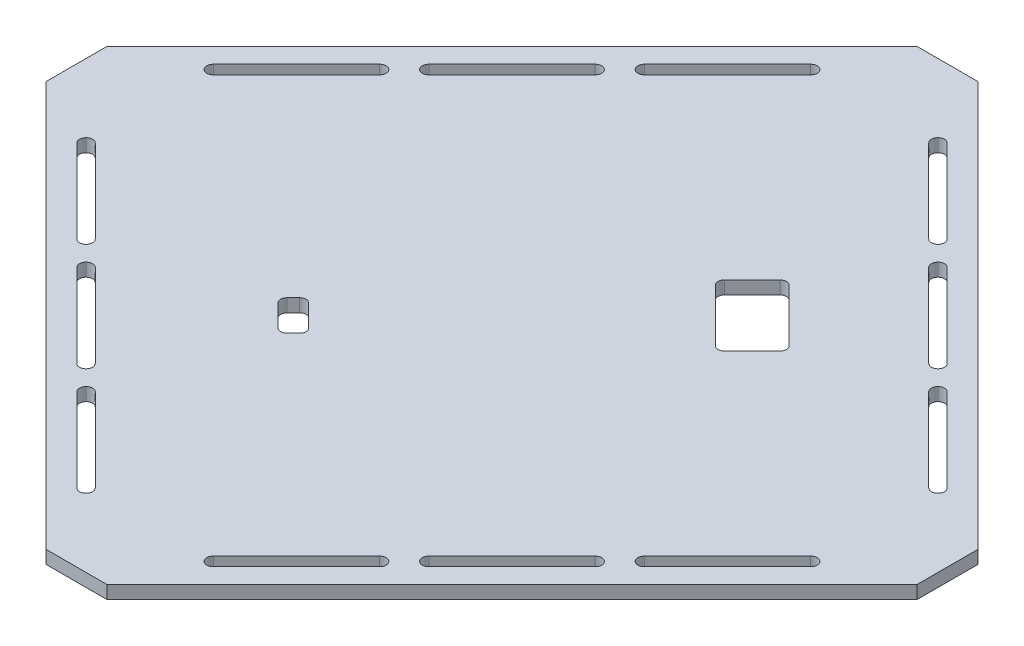
SolidWorks part; units mm, degrees
other "Top Plate" parameters "D1"=4.9724, "D2"=36.4956, "D3"=27.5828, "D4"=37.1524, "D5"=11.2108, "D6"=6.5652, "D8"=3.8454, "D7"=4
ref_plane "Front Plane" through (0, 0, 0) normal (0, 0, 1) x (1, 0, 0)
ref_plane "Top Plane" through (0, 0, 0) normal (0, 1, 0) x (1, 0, 0)
ref_plane "Right Plane" through (0, 0, 0) normal (1, 0, 0) x (0, 0, -1)
sketch "Sketch1" plane through (0, 0, 0) normal (0, 1, 0) x (1, 0, 0)
  line L0 (-7, 100) -> (7, 100)
  line L1 (7, 100) -> (100, 7)
  line L2 (100, 7) -> (100, -7)
  line L3 (100, -7) -> (7, -100)
  line L4 (7, -100) -> (-7, -100)
  line L5 (-7, -100) -> (-100, -7)
  line L6 (-100, -7) -> (-100, 7)
  line L7 (-100, 7) -> (-7, 100)
  point P11 (0, 100)
  point P13 (100, 0)
  dimension "D1" = 200
  dimension "D2" = 200
  dimension "D3" = 14
extrude "Main Plate" add sketch "Sketch1" along normal blind 3 contours L1 L2 L3 L4 L5 L6 L7 L0
sketch "Sketch2" plane through (0, 0, 0) normal (0, -1, 0) x (1, 0, 0)
  line L0 (7.7782, 16.9706) -> (16.9706, 7.7782)
  line L3 (16.9706, 7.7782) -> (19.0919, 9.8995)
  line L6 (19.0919, 9.8995) -> (9.8995, 19.0919)
  line L7 (9.8995, 19.0919) -> (7.7782, 16.9706)
  line L8 (0, 0) -> (53.5, 53.5) construction
  line L9 (100, 7) -> (7, 100) construction
  line L10 (16.9706, -7.7782) -> (7.7782, -16.9706)
  line L11 (9.8995, -19.0919) -> (19.0919, -9.8995)
  line L12 (19.0919, -9.8995) -> (16.9706, -7.7782)
  line L13 (7.7782, -16.9706) -> (9.8995, -19.0919)
  line L14 (-7.7782, -16.9706) -> (-16.9706, -7.7782)
  line L15 (-19.0919, -9.8995) -> (-9.8995, -19.0919)
  line L16 (-9.8995, -19.0919) -> (-7.7782, -16.9706)
  line L17 (-16.9706, -7.7782) -> (-19.0919, -9.8995)
  line L18 (-16.9706, 7.7782) -> (-7.7782, 16.9706)
  line L19 (-9.8995, 19.0919) -> (-19.0919, 9.8995)
  line L20 (-19.0919, 9.8995) -> (-16.9706, 7.7782)
  line L21 (-7.7782, 16.9706) -> (-9.8995, 19.0919)
  point P8 (14.4957, 14.4957)
  point P9 (12.3744, 12.3744)
  point P26 (0, 0)
  dimension "D1" = 3
  dimension "D2" = 13
  dimension "D3" = 17.5
  dimension "D4" = 4
extrude "Bottom Plate Connectors" add sketch "Sketch2" along normal blind 22
fillet "Remove Stress Concentrations" radius 2.5 12 edges at (-14.4957, 0, -14.4957) (-18.0312, 0, -8.8388) (-18.0312, 0, 8.8388) (8.8388, 0, 18.0312) (-14.4957, 0, 14.4957) (-8.8388, 0, 18.0312) (14.4957, 0, 14.4957) (18.0312, 0, -8.8388) (18.0312, 0, 8.8388) (-8.8388, 0, -18.0312) (14.4957, 0, -14.4957) (8.8388, 0, -18.0312)
sketch "Sketch3" plane through (0, 0, 0) normal (0, -1, 0) x (1, 0, 0)
  line L0 (30.4056, -16.2635) -> (38.8909, -24.7487)
  line L1 (38.8909, -24.7487) -> (24.7487, -38.8909)
  line L2 (24.7487, -38.8909) -> (16.2635, -30.4056)
  line L3 (16.2635, -30.4056) -> (30.4056, -16.2635)
  line L4 (16.2635, -16.2635) -> (53.5, -53.5) construction
  line L5 (22.6274, -9.8995) -> (9.8995, -22.6274) construction
  line L6 (7, -100) -> (100, -7) construction
  line L7 (-23.3345, 30.4056) -> (-19.799, 26.8701)
  line L8 (-19.799, 26.8701) -> (-26.8701, 19.799)
  line L9 (-26.8701, 19.799) -> (-30.4056, 23.3345)
  line L10 (-30.4056, 23.3345) -> (-23.3345, 30.4056)
  line L11 (-16.2635, 16.2635) -> (-53.5, 53.5) construction
  line L12 (-22.6274, 9.8995) -> (-9.8995, 22.6274) construction
  line L13 (-7, 100) -> (-100, 7) construction
  point P10 (23.3345, -23.3345)
  point P21 (-23.3345, 23.3345)
  dimension "D1" = 20
  dimension "D2" = 12
  dimension "D3" = 10
  dimension "D4" = 10
  dimension "D5" = 5
  dimension "D6" = 10
extrude "Wire Holes" cut sketch "Sketch3" against normal through all
sketch "Sketch4" plane through (0, 3, 0) normal (0, 1, 0) x (1, 0, 0)
  line L0 (14.6091, 85.3198) -> (35.8223, 64.1066)
  line L1 (35.8223, 64.1066) -> (33.701, 61.9853)
  line L2 (33.701, 61.9853) -> (12.4878, 83.1985)
  line L3 (12.4878, 83.1985) -> (14.6091, 85.3198)
  line L4 (39.3579, 60.5711) -> (60.5711, 39.3579)
  line L5 (60.5711, 39.3579) -> (58.4497, 37.2365)
  line L6 (58.4497, 37.2365) -> (37.2365, 58.4497)
  line L7 (37.2365, 58.4497) -> (39.3579, 60.5711)
  line L8 (64.1066, 35.8223) -> (85.3198, 14.6091)
  line L9 (85.3198, 14.6091) -> (83.1985, 12.4878)
  line L10 (83.1985, 12.4878) -> (61.9853, 33.701)
  line L11 (61.9853, 33.701) -> (64.1066, 35.8223)
  line L12 (0, 0) -> (53.5, 53.5) construction
  line L13 (7, 100) -> (100, 7) construction
  line L14 (85.3198, -14.6091) -> (64.1066, -35.8223)
  line L15 (83.1985, -12.4878) -> (85.3198, -14.6091)
  line L16 (61.9853, -33.701) -> (83.1985, -12.4878)
  line L17 (64.1066, -35.8223) -> (61.9853, -33.701)
  line L18 (58.4497, -37.2365) -> (60.5711, -39.3579)
  line L19 (60.5711, -39.3579) -> (39.3579, -60.5711)
  line L20 (37.2365, -58.4497) -> (58.4497, -37.2365)
  line L21 (39.3579, -60.5711) -> (37.2365, -58.4497)
  line L22 (33.701, -61.9853) -> (35.8223, -64.1066)
  line L23 (35.8223, -64.1066) -> (14.6091, -85.3198)
  line L24 (12.4878, -83.1985) -> (33.701, -61.9853)
  line L25 (14.6091, -85.3198) -> (12.4878, -83.1985)
  line L26 (-14.6091, -85.3198) -> (-35.8223, -64.1066)
  line L27 (-12.4878, -83.1985) -> (-14.6091, -85.3198)
  line L28 (-33.701, -61.9853) -> (-12.4878, -83.1985)
  line L29 (-35.8223, -64.1066) -> (-33.701, -61.9853)
  line L30 (-37.2365, -58.4497) -> (-39.3579, -60.5711)
  line L31 (-39.3579, -60.5711) -> (-60.5711, -39.3579)
  line L32 (-58.4497, -37.2365) -> (-37.2365, -58.4497)
  line L33 (-60.5711, -39.3579) -> (-58.4497, -37.2365)
  line L34 (-61.9853, -33.701) -> (-64.1066, -35.8223)
  line L35 (-64.1066, -35.8223) -> (-85.3198, -14.6091)
  line L36 (-83.1985, -12.4878) -> (-61.9853, -33.701)
  line L37 (-85.3198, -14.6091) -> (-83.1985, -12.4878)
  line L38 (-85.3198, 14.6091) -> (-64.1066, 35.8223)
  line L39 (-83.1985, 12.4878) -> (-85.3198, 14.6091)
  line L40 (-61.9853, 33.701) -> (-83.1985, 12.4878)
  line L41 (-64.1066, 35.8223) -> (-61.9853, 33.701)
  line L42 (-58.4497, 37.2365) -> (-60.5711, 39.3579)
  line L43 (-60.5711, 39.3579) -> (-39.3579, 60.5711)
  line L44 (-37.2365, 58.4497) -> (-58.4497, 37.2365)
  line L45 (-39.3579, 60.5711) -> (-37.2365, 58.4497)
  line L46 (-33.701, 61.9853) -> (-35.8223, 64.1066)
  line L47 (-35.8223, 64.1066) -> (-14.6091, 85.3198)
  line L48 (-12.4878, 83.1985) -> (-33.701, 61.9853)
  line L49 (-14.6091, 85.3198) -> (-12.4878, 83.1985)
  point P17 (47.8431, 47.8431)
  point P57 (0, 0)
  dimension "D1" = 3
  dimension "D2" = 30
  dimension "D3" = 30
  dimension "D4" = 30
  dimension "D5" = 5
  dimension "D6" = 5
  dimension "D8" = 5
extrude "Cut-Extrude1" cut sketch "Sketch4" against normal through all
fillet "Fillet1" radius 1.5 56 edges at (16.2635, 1.5, -30.4056) (24.7487, 1.5, -38.8909) (30.4056, 1.5, -16.2635) (38.8909, 1.5, -24.7487) (-23.3345, 1.5, 30.4056) (-19.799, 1.5, 26.8701) (-30.4056, 1.5, 23.3345) (-26.8701, 1.5, 19.799) (-33.701, 1.5, 61.9853) (-58.4497, 1.5, 37.2365) (-83.1985, 1.5, 12.4878) (-64.1066, 1.5, -35.8223) (-39.3579, 1.5, -60.5711) (-14.6091, 1.5, -85.3198) (14.6091, 1.5, -85.3198) (33.701, 1.5, 61.9853) (58.4497, 1.5, 37.2365) (83.1985, 1.5, 12.4878) (39.3579, 1.5, -60.5711) (64.1066, 1.5, -35.8223) (-39.3579, 1.5, 60.5711) (-64.1066, 1.5, 35.8223) (-83.1985, 1.5, -12.4878) (-58.4497, 1.5, -37.2365) (-33.701, 1.5, -61.9853) (33.701, 1.5, -61.9853) (58.4497, 1.5, -37.2365) (83.1985, 1.5, -12.4878) (64.1066, 1.5, 35.8223) (-14.6091, 1.5, 85.3198) (39.3579, 1.5, 60.5711) (14.6091, 1.5, 85.3198) (-85.3198, 1.5, 14.6091) (-85.3198, 1.5, -14.6091) (-60.5711, 1.5, -39.3579) (-35.8223, 1.5, -64.1066) (-60.5711, 1.5, 39.3579) (-35.8223, 1.5, 64.1066) (12.4878, 1.5, 83.1985) (12.4878, 1.5, -83.1985) (-12.4878, 1.5, 83.1985) (-37.2365, 1.5, 58.4497) (-61.9853, 1.5, 33.701) (-61.9853, 1.5, -33.701) (-37.2365, 1.5, -58.4497) (-12.4878, 1.5, -83.1985) (35.8223, 1.5, -64.1066) (60.5711, 1.5, -39.3579) (85.3198, 1.5, -14.6091) (35.8223, 1.5, 64.1066) (60.5711, 1.5, 39.3579) (85.3198, 1.5, 14.6091) (37.2365, 1.5, 58.4497) (61.9853, 1.5, 33.701) (37.2365, 1.5, -58.4497) (61.9853, 1.5, -33.701)
equation "\"D3@Sketch4\"=\"D2@Sketch4\""
equation "\"D4@Sketch4\"=\"D2@Sketch4\""
